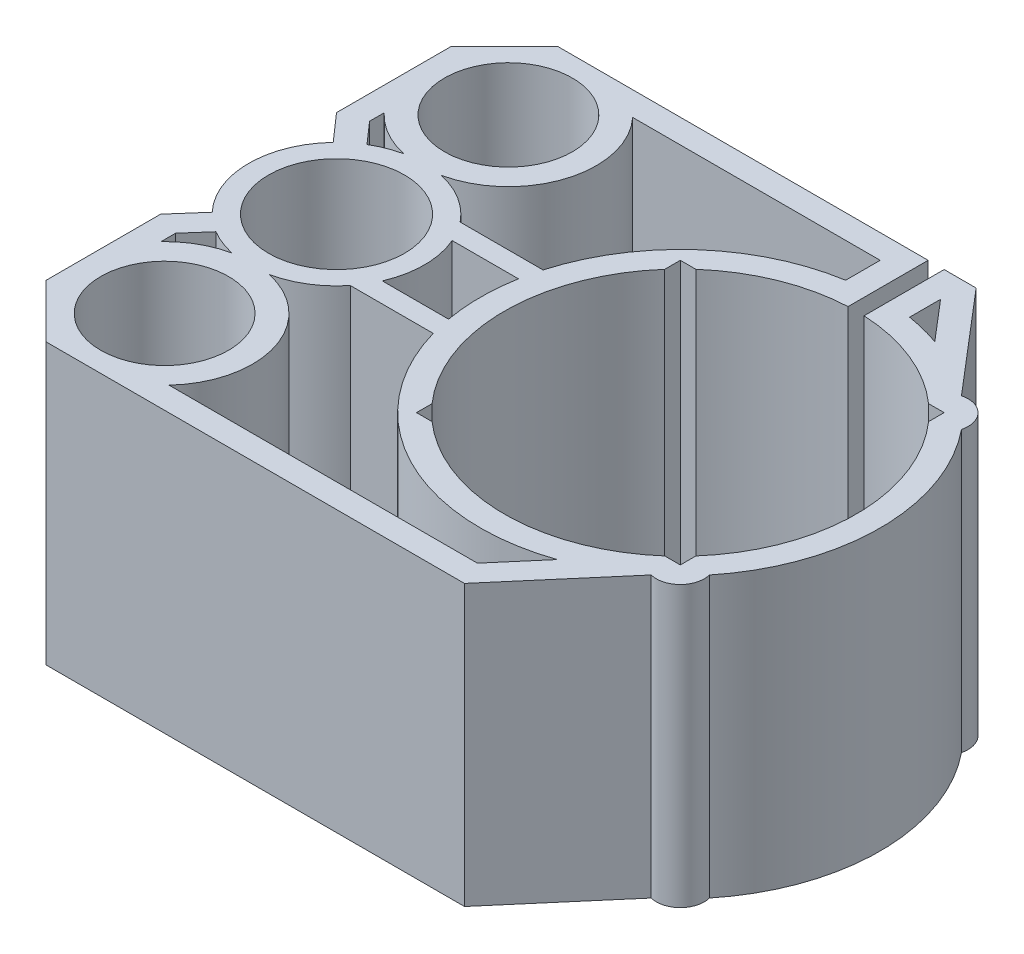
SolidWorks part; units mm, degrees
ref_plane "Front Plane" through (0, 0, 0) normal (0, 0, 1) x (1, 0, 0)
ref_plane "Top Plane" through (0, 0, 0) normal (0, 1, 0) x (1, 0, 0)
ref_plane "Right Plane" through (0, 0, 0) normal (1, 0, 0) x (0, 0, -1)
sketch "Sketch1" plane through (0, 0, 0) normal (0, 1, 0) x (1, 0, 0)
  line L0 (0, 0) -> (0, 16.5) construction
  line L1 (0, 16.5) -> (16.5, 16.5) construction
  line L2 (16.5, 16.5) -> (-16.5, -16.5) construction
  line L3 (0, 22) -> (0, 32) construction
  line L4 (16.5, 16.5) -> (-16.5, 16.5)
  line L5 (16.5, 16.5) -> (16.5, -16.5)
  line L6 (16.5, -16.5) -> (-16.5, -16.5)
  line L7 (-16.5, 16.5) -> (-16.5, -16.5)
  line L8 (1, 22) -> (1, 32)
  line L9 (-1, 22) -> (-1, 32)
  line L10 (1, 32) -> (5, 32)
  line L11 (5, 32) -> (15.7595, 19.4072)
  line L12 (18.6213, 18.6213) -> (16.5, 16.5) construction
  line L13 (4, 21.6333) -> (4, 28.5521)
  line L14 (-34.9533, 29) -> (-23.2995, 29)
  line L15 (4, 28.5521) -> (13.6619, 17.2439)
  line L16 (5, -32) -> (15.7595, -19.4072)
  line L17 (0, 0) -> (0, -25) construction
  line L18 (0, -25) -> (0, -32) construction
  line L19 (0, -32) -> (5, -32)
  line L20 (0, -32) -> (-23.2995, -32)
  line L21 (-1, 32) -> (-23.2995, 32)
  line L22 (0, -29) -> (-23.2995, -29)
  line L23 (0, -29) -> (3.6179, -29)
  line L24 (3.6179, -29) -> (13.6638, -17.2424)
  line L25 (-4, 22) -> (-4, 29)
  line L26 (-4, 29) -> (-23.2995, 29)
  line L27 (-23.2995, 32) -> (-23.2995, 29)
  line L28 (-23.2995, -29) -> (-23.2995, -32)
  line L29 (0, -29) -> (0, -25)
  line L30 (-3, -29) -> (-3, -24.8193)
  line L31 (1, 22) -> (1, 21.9773)
  line L32 (-1, 22) -> (-1, 21.9773)
  line L33 (-23.2995, -32) -> (-47.3408, -32)
  line L34 (-47.3408, -32) -> (-54, -25.3408)
  line L35 (-54, -25.3408) -> (-54, -11)
  line L36 (-54, -11) -> (-43, 0) construction
  line L37 (0, 0) -> (-43, 0) construction
  line L38 (-43, -32) -> (-43, 0) construction
  line L39 (-43, -21.5) -> (-54, -21.5) construction
  line L40 (-43, -21.5) -> (-50.6704, -28.6704) construction
  line L41 (-50.9825, -7.5683) -> (-54, -11)
  line L42 (-16.5, -29) -> (-16.5, -18.7816)
  line L43 (-19, -29) -> (-19, -16.2481)
  line L44 (-23.2995, -29) -> (-34.9533, -29)
  line L45 (-48.6381, -9.4452) -> (-51, -12.1314)
  line L46 (-51, -12.1314) -> (-51, -13.9502)
  line L47 (-24.0375, -6.8703) -> (-34.4094, -6.8703)
  line L48 (-32.9054, -4.3703) -> (-24.615, -4.3703)
  line L49 (-23.2995, 32) -> (-47.3408, 32)
  line L50 (-32.9054, 4.3703) -> (-24.615, 4.3703)
  line L51 (-50.9825, 7.5683) -> (-54, 11)
  line L52 (-48.6381, 9.4452) -> (-51, 12.1314)
  line L53 (-51, 12.1314) -> (-51, 13.9502)
  line L54 (-54, 25.3408) -> (-54, 11)
  line L55 (-47.3408, 32) -> (-54, 25.3408)
  line L56 (15.6445, -19.5504) -> (5, -32) construction
  line L57 (13.3643, -17.6008) -> (3.6179, -29) construction
  line L58 (-24.0375, 6.8703) -> (-34.4094, 6.8703)
  circle A0 centre (0, 0) radius 25
  circle A1 centre (0, 0) radius 22
  arc A2 (15.7595, -19.4072) -> (19.4072, -15.7595) centre (16.5, -16.5) ccw
  arc A3 (15.7595, 19.4072) -> (19.4072, 15.7595) centre (16.5, 16.5) cw
  arc A5 (-34.9533, -29) -> (-54, -21.5) centre (-43, -21.5) ccw
  circle A6 centre (-43, -21.5) radius 8
  circle A7 centre (-43, 0) radius 8.5
  circle A8 centre (-43, 0) radius 11
  arc A11 (-34.9533, 29) -> (-54, 21.5) centre (-43, 21.5) cw
  circle A12 centre (-43, 21.5) radius 8
  point P24 (0, 0)
  point P58 (-43, -29.5)
  point P60 (-51, -21.5)
  point P61 (-48.8441, -26.9632)
  point P69 (-16.5, -23.8908)
  point P73 (-43, -13.5)
  point P75 (-43, -8.5)
  point P76 (0, -22)
  point P77 (-35, -21.5)
  point P80 (-32.9054, -4.3703)
  point P81 (-24.615, -4.3703)
  dimension "D1" = 50
  dimension "D6" = 3
  dimension "D17" = 17
  dimension "D18" = 16
  dimension "D24" = 2.5
  dimension "D26" = 3
  dimension "D29" = 37.5
  dimension "D12" = 3
  dimension "D3" = 16.5
  dimension "D4" = 16.5
  dimension "D5" = 46.669
  dimension "D8" = 10
  dimension "D11" = 4
  dimension "D13" = 10
  dimension "D16" = 3
  dimension "D19" = 2.5
  dimension "D20" = 3
  dimension "D21" = 135
  dimension "D22" = 2.5
  dimension "D23" = 45
  dimension "D25" = 2.5
  dimension "D27" = 3
  dimension "D28" = 3
  dimension "D30" = 2.5
  dimension "D7" = 3
  dimension "D2" = 3
  dimension "D9" = 1
  dimension "D10" = 1
  dimension "D14" = 3
  dimension "D15" = 3
extrude "Boss-Extrude1" add sketch "Sketch1" along normal blind 35 contours A0 L11 L10 L8 L13 L15 | A1 L13 A0 L8 L31 | A1 L15 A0 L13 | A1 L5 L6 L24 A0 L15 L4 | A1 L32 L9 A0 L24 L6 L7 L4 | A3 A0 | A0 A2 | A0 L24 L23 L22 L28 L20 L19 L16 | A8 L47 A0 L48 | A8 A5 L35 L34 L33 L28 L44 A6 | A0 L9 L21 L27 L26 L25 | A5 A8 | A8 A11 A5 A7 | A11 A8 L14 L27 L49 L55 L54 A12 | A11 A8 | A8 L50 A0 L58 | A8 L41 L35 A5 L46 L45 | L53 A11 L54 L51 A8 L52 region at (15.5258, 0, -17.0011) region at (-15.5258, 0, -17.1319) region at (7.5368, 0, -21.8891) region at (5.9588, 0, -27.1719) region at (2.5035, 0, -23.3494) region at (18.045, 0, -18.045) region at (-10.6415, 0, -29.9407) region at (-4.4132, 0, 29.2881) region at (18.045, 0, 18.045) region at (-23.6729, 0, -30.5) region at (-28.9739, 0, -5.6671) region at (-33.8377, 0, -5.5118) region at (-43, 0, -10.75) region at (-28.9739, 0, 5.6671) region at (-35.3202, 0, 31.6266) region at (-52.1214, 0, -12.3199) region at (-43, 0, 10.75) region at (-52.1214, 0, 12.3199)
ref_plane "Plane1" through (19.4072, 0, 0) normal (-1, 0, 0) x (0, 0, 1)
sketch "Sketch4" plane through (4, 0, 0) normal (1, 0, 0) x (0, 0, -1)
  line L4 (24.6779, 0) -> (28.5521, 0)
  line L5 (24.6779, 23.5) -> (28.5521, 23.5)
  line L6 (24.6779, 23.5) -> (24.6779, 11.5)
  line L7 (24.6779, 11.5) -> (28.5521, 11.5)
  line L8 (24.6779, 0) -> (28.5521, 0)
  line L9 (28.5521, 0) -> (28.5521, 35)
  line L10 (28.5521, 35) -> (24.6779, 35)
  line L11 (24.6779, 35) -> (24.6779, 0)
  line L12 (28.5521, 35) -> (24.6779, 35)
  line L13 (28.5521, 0) -> (28.5521, 35) construction
  line L15 (24.6779, 35) -> (24.6779, 0) construction
  line L16 (28.5521, 23.5) -> (28.5521, 11.5)
  point P6 (24.6779, 17.5)
  dimension "D2" = 12
  dimension "D1" = 0
ref_plane "Plane2" through (0, 23.5, 0) normal (0, -1, 0) x (0, 0, -1)
ref_plane "Plane3" through (0, 11.5, 0) normal (0, -1, 0) x (0, 0, -1)
sketch "Sketch6" plane through (0, 23.5, 0) normal (0, -1, 0) x (0, 0, -1)
  line L0 (30.7174, 3.9637) -> (22.7854, 3.9637)
  line L1 (22.7854, 3.9637) -> (22.7854, 10.6041)
  line L2 (22.7854, 10.6041) -> (30.7174, 3.9637)
extrude "Boss-Extrude3" add sketch "Sketch6" along normal up to surface (12 mm away) up to plane "Plane3"
sketch "Sketch3" plane through (19.4072, 0, 0) normal (-1, 0, 0) x (0, 0, 1)
  line L0 (-32, 17.5) -> (-27, 17.5) construction
  line L1 (-32, 35) -> (-32, 0) construction
  line L2 (-27, 17.5) -> (-27, 13.5) construction
  line L3 (-32, 17.5) -> (-32, 21.5) construction
  line L5 (-32, 21.5) -> (-27, 21.5)
  line L6 (-32, 21.5) -> (-32, 13.5)
  line L7 (-32, 13.5) -> (-27, 13.5)
  line L8 (-27, 21.5) -> (-27, 13.5)
  circle A0 centre (-27, 17.5) radius 4
  dimension "D1" = 5
  dimension "D2" = 4
  dimension "D3" = 4
extrude "Cut-Extrude1" cut sketch "Sketch3" along normal up to vertex (14.4072 mm away) contours L8 A0 | L8 A0 | A0 L5 L6 L7 region at (19.4072, 21.4057, -29.5) region at (19.4072, 17.5, -25.3023) region at (19.4072, 17.5, -28.6977) up to point (5, 35, -32)
sketch "Sketch7" plane through (0, 0, 0) normal (0, -1, 0) x (1, 0, 0)
  line L0 (-43, 0) -> (-48.646, -5.6677) construction
  circle A0 centre (-43, 0) radius 5
  circle A1 centre (-43, 0) radius 6.165
  circle A2 centre (-43, 0) radius 8.5
  circle A3 centre (-43, 0) radius 8
  circle A4 centre (-48.646, -5.6677) radius 1.425
  circle A5 centre (-48.6569, 5.6569) radius 1.425
  circle A6 centre (-37.3323, 5.6677) radius 1.425
  circle A7 centre (-37.3215, -5.6568) radius 1.425
  point P17 (-42.9892, 0)
  dimension "D1" = 10
  dimension "D2" = 12.33
  dimension "D3" = 16
  dimension "D4" = 2.85
  dimension "D5" = 4
extrude "Boss-Extrude4" add sketch "Sketch7" against normal blind 15 contours A2
extrude "Cut-Extrude2" cut sketch "Sketch7<3>" against normal blind 15 contours A0
sketch "Sketch7<3>" plane through (0, 0, 0) normal (0, -1, 0) x (1, 0, 0) same geometry as "Sketch7"
extrude "Cut-Extrude3" cut sketch "Sketch7<4>" against normal blind 1.5 contours A1
sketch "Sketch7<4>" plane through (0, 0, 0) normal (0, -1, 0) x (1, 0, 0) same geometry as "Sketch7"
extrude "Cut-Extrude4" cut sketch "Sketch7<5>" against normal blind 8 contours A4 | A5 | A6 | A7
sketch "Sketch7<5>" plane through (0, 0, 0) normal (0, -1, 0) x (1, 0, 0) same geometry as "Sketch7"
